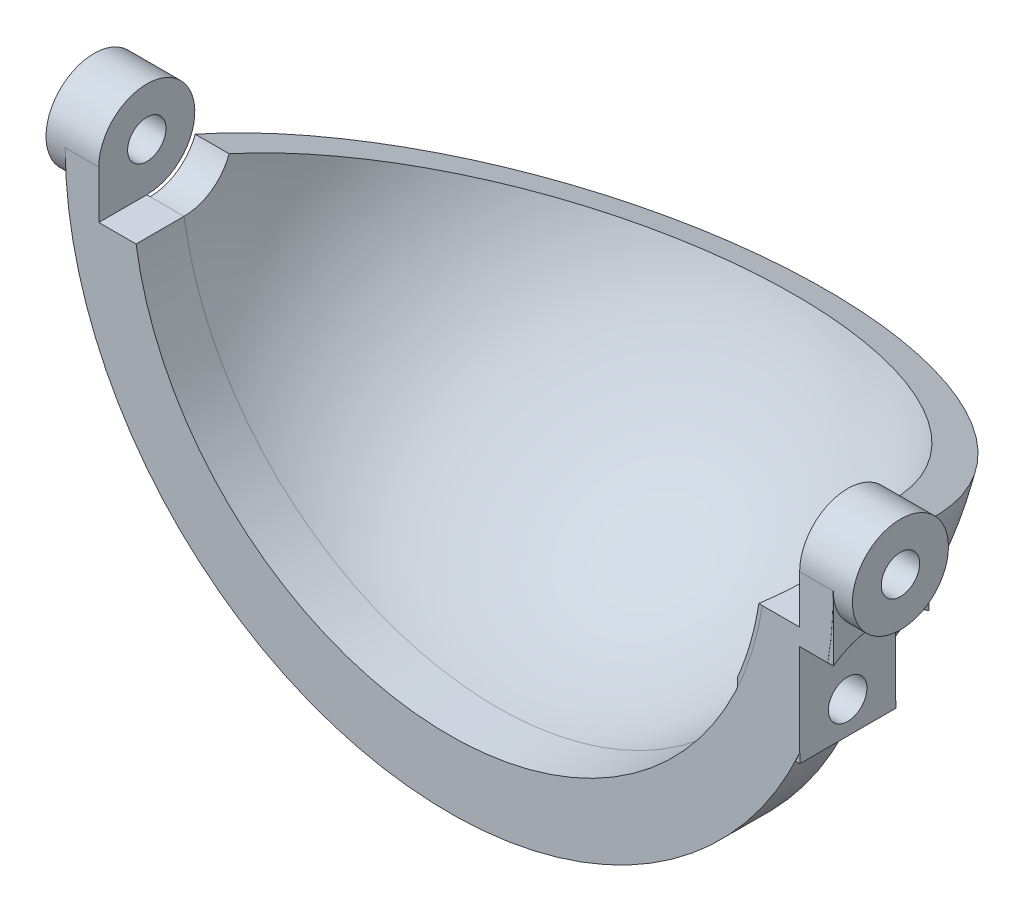
SolidWorks part; units mm, degrees
ref_plane "前视基准面" through (0, 0, 0) normal (0, 0, 1) x (1, 0, 0)
ref_plane "上视基准面" through (0, 0, 0) normal (0, 1, 0) x (1, 0, 0)
ref_plane "右视基准面" through (0, 0, 0) normal (1, 0, 0) x (0, 0, -1)
sketch "草图1" plane through (0, 0, 0) normal (0, 0, 1) x (1, 0, 0)
  line L0 (20, 0) -> (-20, 0) construction
  line L1 (-20, 0) -> (-16.5, 0)
  line L2 (16.5, 0) -> (20, 0)
  circle A0 centre (0, 0) radius 20 construction
  circle A1 centre (0, 0) radius 16.5 construction
  arc A2 (-20, 0) -> (20, 0) centre (0, 0) ccw
  arc A3 (-16.5, 0) -> (16.5, 0) centre (0, 0) ccw
  dimension "D1" = 33
  dimension "D2" = 40
extrude "凸台-拉伸1" add sketch "草图1" along normal blind 2.5
sketch "草图2" plane through (0, 0, 0) normal (0, 0, -1) x (-1, 0, 0)
  line L0 (-16.5, 0) -> (16.5, 0) construction
  line L1 (16.5, 0) -> (20, 0) construction
  line L2 (-20, 0) -> (-16.5, 0) construction
  line L3 (-18.25, 0) -> (-16.5, 0)
  line L4 (18.25, 0) -> (16.5, 0)
  arc A0 (-16.5, 0) -> (16.5, 0) centre (0, 0) ccw
  arc A2 (18.25, 0) -> (-18.25, 0) centre (0, 0) cw
revolve "旋转1" add sketch "草图2" angle 70 about L0 reverse direction yes
sketch "草图4" plane through (0, 0, 0) normal (1, 0, 0) x (0, 0, -1)
  circle A0 centre (0, 0) radius 1
  circle A1 centre (0, 0) radius 2.5
extrude "凸台-拉伸2" add sketch "草图4" along normal blind 20 and the other way blind 20
sketch "草图5" plane through (0, 0, 0) normal (1, 0, 0) x (0, 0, -1)
  line L0 (0, -2.5) -> (-2.5, -2.5)
  line L1 (-2.5, 0) -> (-2.5, -20) construction
  line L2 (-2.5, -2.5) -> (-2.5, 0)
  circle A0 centre (0, 0) radius 1
  circle A1 centre (0, 0) radius 2.5 construction
  arc A2 (-2.5, 0) -> (0, -2.5) centre (0, 0) cw
extrude "切除-拉伸1" cut sketch "草图5" against normal blind 18.25 and the other way blind 18.25
sketch "草图6" plane through (20, 0, 0) normal (1, 0, 0) x (0, 0, -1)
  circle A0 centre (0, 0) radius 1
extrude "切除-拉伸2" cut sketch "草图6" against normal blind 100
sketch "草图8" plane through (20, 0, 0) normal (1, 0, 0) x (0, 0, -1)
  line L0 (0, 0) -> (0, -7) construction
  line L1 (-2.4945, -0.166) -> (-2.4945, -8.666)
  line L2 (-2.4945, -8.666) -> (2.5055, -8.666)
  line L3 (2.5055, -8.666) -> (2.4945, 0.166)
  circle A0 centre (0, -7) radius 1
  arc A1 (2.4945, 0.166) -> (-2.4945, -0.166) centre (0, 0) cw
  circle A2 centre (0, 0) radius 2.5 construction
  circle M4 centre (0, 0) radius 2.5
extrude "凸台-拉伸3" add sketch "草图8" against normal blind 5 contours L2 L3 A1 A0 L1 M4 region at (20, -5.118, -0.004)
sketch "草图9" plane through (20, 0, 0) normal (1, 0, 0) x (0, 0, -1)
  circle A0 centre (0, -7) radius 1.0046
extrude "切除-拉伸3" cut sketch "草图9" against normal blind 10
sketch "草图10" plane through (-20, 0, 0) normal (-1, 0, 0) x (0, 0, 1)
  circle A0 centre (0, 0) radius 1
  circle A1 centre (0, 0) radius 2.5
extrude "凸台-拉伸4" add sketch "草图10" along normal blind 1
sketch "草图11" plane through (20, 0, 0) normal (1, 0, 0) x (0, 0, -1)
  circle A0 centre (0, 0) radius 1
  circle A1 centre (0, 0) radius 2.5
extrude "凸台-拉伸5" add sketch "草图11" along normal blind 1
sketch "草图12" plane through (0, 0, 0) normal (0, 0, 1) x (1, 0, 0)
  line L0 (-16.5, 0) -> (16.5, 0)
  arc A1 (-16.5, 0) -> (16.5, 0) centre (0, 0) ccw
revolve "切除-旋转1" cut sketch "草图12" angle 360 about L0
sketch "草图13" plane through (0, 0.0031, -2.4947) normal (0, 0.0012, -1) x (-1, 0, 0)
  line L1 (-18.25, -0.1628) -> (-6.5639, -0.1628)
  line L2 (-18.25, -0.1628) -> (-18.25, -0.9322)
  line L3 (-18.25, -0.9322) -> (-6.5639, -0.9322)
  line L4 (-6.5639, -0.1628) -> (-6.5639, -0.9322)
extrude "切除-拉伸4" cut sketch "草图13" against normal blind 10
sketch "草图14" plane through (18.25, 0, 0) normal (-1, 0, 0) x (0, 0, 1)
  line L1 (-0.0031, 0) -> (2.5, 0)
  line L2 (-0.0031, 0) -> (-0.0031, -2.5)
  line L3 (-0.0031, -2.5) -> (2.5, -2.5)
  line L4 (2.5, 0) -> (2.5, -2.5)
  arc A0 (-2.3209, -0.9293) -> (2.3185, -0.9351) centre (0, 0) ccw construction
  point P5 (-0.0031, -2.5)
extrude "切除-拉伸5" cut sketch "草图14" along normal blind 10
sketch "草图15" plane through (20, 0, 0) normal (1, 0, 0) x (0, 0, -1)
  circle A0 centre (0, -7) radius 1.0046
  circle A1 centre (0, -7) radius 4.4
extrude "切除-拉伸7" cut sketch "草图15" against normal blind 1.75 contours A1
